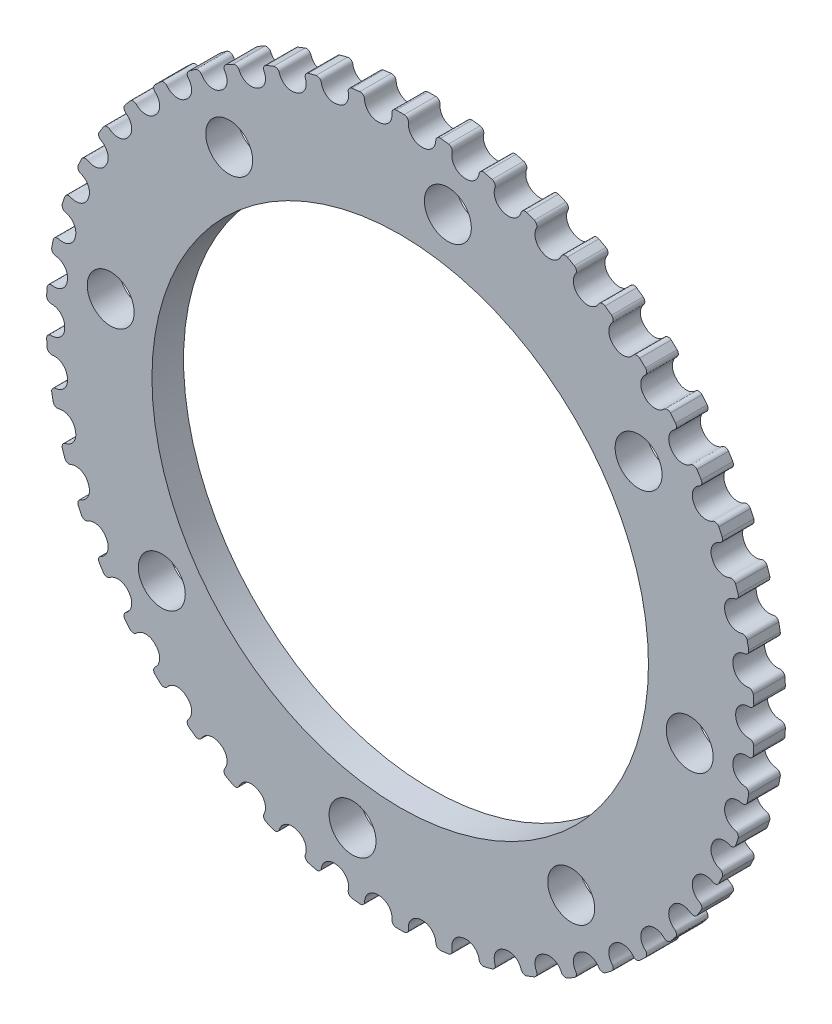
SolidWorks part; units mm, degrees
material "Thornel Mat VMA"
ref_plane "Front Plane" through (0, 0, 0) normal (0, 0, 1) x (1, 0, 0)
ref_plane "Top Plane" through (0, 0, 0) normal (0, 1, 0) x (1, 0, 0)
ref_plane "Right Plane" through (0, 0, 0) normal (1, 0, 0) x (0, 0, -1)
ref_axis "Axis1" through (0, 0, 55) along (0, 0, -1)
sketch "SketchRevolveGearBelt01" plane through (0, 0, 0) normal (1, 0, 0) x (0, 0, -1)
  line L0 (0, 0) -> (1, 0) construction
  line L1 (1.75, 0) -> (1.75, 39.2172)
  line L2 (1.75, 39.2172) -> (-1.75, 39.2172)
  line L3 (-1.75, 39.2172) -> (-1.75, 0)
  line L4 (-1.75, 0) -> (1.75, 0)
  dimension "GearBeltSide1" = 1.75
  dimension "GearBeltOutsideDiameter" = 39.2172
  dimension "GearBeltSide2" = 1.75
revolve "GearBelt01" add sketch "SketchRevolveGearBelt01" angle 360 about L0
sketch "SketchToothGearBelt01" plane through (0, 0, 0) normal (0, 0, 1) x (1, 0, 0)
  arc A0 (39.1647, 2.0323) -> (39.1647, -2.0323) centre (0, 0) cw
  spline S0 degree 3 poles (39.1647, -2.0323) (39.166, -2.006) (39.1649, -1.9663) (39.1569, -1.9141) (39.1478, -1.8755) (39.1356, -1.8378) (39.1204, -1.8013) (39.1023, -1.7661) (39.0814, -1.7324) (39.0578, -1.7006) (39.0317, -1.6708) (39.0033, -1.6432) (38.9728, -1.618) (38.9403, -1.5953) (38.9061, -1.5754) (38.8703, -1.5582) (38.8333, -1.5441) (38.7953, -1.533) (38.7565, -1.525) (38.7172, -1.5201) (38.6658, -1.5185) (38.59, -1.5198) (38.4897, -1.516) (38.3775, -1.5026) (38.2667, -1.4805) (38.158, -1.4498) (38.052, -1.4107) (37.9494, -1.3633) (37.8509, -1.3081) (37.7569, -1.2453) (37.6682, -1.1753) (37.5853, -1.0986) (37.5086, -1.0156) (37.4387, -0.9268) (37.376, -0.8329) (37.3208, -0.7343) (37.2735, -0.6317) (37.2344, -0.5257) (37.2037, -0.4169) (37.1817, -0.3061) (37.1683, -0.1939) (37.1652, -0.1051) (37.1655, -0.0405) (37.1655, 0) (37.1655, 0.0405) (37.1652, 0.1051) (37.1683, 0.1939) (37.1817, 0.3061) (37.2037, 0.4169) (37.2344, 0.5257) (37.2735, 0.6317) (37.3208, 0.7343) (37.376, 0.8329) (37.4387, 0.9268) (37.5086, 1.0156) (37.5853, 1.0986) (37.6682, 1.1753) (37.7569, 1.2453) (37.8509, 1.3081) (37.9494, 1.3633) (38.052, 1.4107) (38.158, 1.4498) (38.2667, 1.4805) (38.3775, 1.5026) (38.4897, 1.516) (38.59, 1.5198) (38.6658, 1.5185) (38.7172, 1.5201) (38.7565, 1.525) (38.7953, 1.533) (38.8333, 1.5441) (38.8703, 1.5582) (38.9061, 1.5754) (38.9403, 1.5953) (38.9728, 1.618) (39.0033, 1.6432) (39.0317, 1.6708) (39.0578, 1.7006) (39.0814, 1.7324) (39.1023, 1.7661) (39.1204, 1.8013) (39.1356, 1.8378) (39.1478, 1.8755) (39.1569, 1.9141) (39.1649, 1.9663) (39.166, 2.006) (39.1647, 2.0323) knots 0 0 0 0 0.012346 0.01852 0.024693 0.030866 0.037039 0.043212 0.049386 0.055559 0.061732 0.067905 0.074078 0.080252 0.086425 0.092598 0.098771 0.104944 0.111118 0.117291 0.123464 0.135171 0.152781 0.17039 0.188 0.205609 0.223219 0.240828 0.258438 0.276048 0.293657 0.311267 0.328876 0.346486 0.364095 0.381705 0.399315 0.416924 0.434534 0.452143 0.469753 0.487362 0.493681 0.5 0.506319 0.512638 0.530247 0.547857 0.565466 0.583076 0.600685 0.618295 0.635905 0.653514 0.671124 0.688733 0.706343 0.723952 0.741562 0.759172 0.776781 0.794391 0.812 0.82961 0.847219 0.864829 0.876536 0.882709 0.888882 0.895056 0.901229 0.907402 0.913575 0.919748 0.925922 0.932095 0.938268 0.944441 0.950614 0.956788 0.962961 0.969134 0.975307 0.98148 0.987654 1 1 1 1
extrude "ToothExtrudeCutGearBelt01" cut sketch "SketchToothGearBelt01" against normal blind 7.239 and the other way blind 7.239
pattern_circular "PatternGearBelt01" count 50 every 7.2 about axis through (0, 0, 55) along (0, 0, -1) of "ToothExtrudeCutGearBelt01"
sketch "BoreRevolveSketch" plane through (0, 0, 0) normal (1, 0, 0) x (0, 0, -1)
  line L0 (0, 0) -> (1, 0) construction
  line L1 (-7.239, 0) -> (7.239, 0)
  line L2 (7.239, 0) -> (7.239, 27.5)
  line L3 (7.239, 27.5) -> (-7.239, 27.5)
  line L4 (-7.239, 27.5) -> (-7.239, 0)
  dimension "BoreSide1" = 7.239
  dimension "TaperSide1" = 27.5
  dimension "BoreSide2" = 7.239
  dimension "TaperSide2" = 27.5
revolve "BoreRevolveCut" cut sketch "BoreRevolveSketch" angle 360 about L0
sketch "AuxiliarySketchGearBelt01" plane through (0, 0, 0) normal (0, 0, 1) x (1, 0, 0)
  circle A0 centre (0, 0) radius 39.7887 construction
  dimension "PitchDiameter" = 79.5774
sketch "Sketch1" plane through (0, 0, 1.75) normal (0, 0, 1) x (1, 0, 0)
  circle A0 centre (5.2787, 32.0684) radius 2 construction
  circle A1 centre (26.4084, 18.9432) radius 2 construction
  circle A2 centre (32.0684, -5.2787) radius 2 construction
  circle A3 centre (18.9432, -26.4084) radius 2 construction
  circle A4 centre (-5.2787, -32.0684) radius 2 construction
  circle A5 centre (-26.4084, -18.9432) radius 2 construction
  circle A6 centre (-32.0684, 5.2787) radius 2 construction
  circle A7 centre (-18.9432, 26.4084) radius 2 construction
  circle A8 centre (5.2787, 32.0684) radius 2 construction
  circle A9 centre (26.4084, 18.9432) radius 2 construction
  circle A10 centre (32.0684, -5.2787) radius 2 construction
  circle A11 centre (18.9432, -26.4084) radius 2 construction
  circle A12 centre (-5.2787, -32.0684) radius 2 construction
  circle A13 centre (-26.4084, -18.9432) radius 2 construction
  circle A14 centre (-32.0684, 5.2787) radius 2 construction
  circle A15 centre (-18.9432, 26.4084) radius 2 construction
  circle A16 centre (-18.9432, 26.4084) radius 2.6
  circle A17 centre (5.2787, 32.0684) radius 2.6
  circle A18 centre (26.4084, 18.9432) radius 2.6
  circle A19 centre (32.0684, -5.2787) radius 2.6
  circle A20 centre (18.9432, -26.4084) radius 2.6
  circle A21 centre (-5.2787, -32.0684) radius 2.6
  circle A22 centre (-32.0684, 5.2787) radius 2.6
  circle A23 centre (-26.4084, -18.9432) radius 2.6
  dimension "D1" = 5.2
extrude "Cut-Extrude1" cut sketch "Sketch1" against normal blind 10
